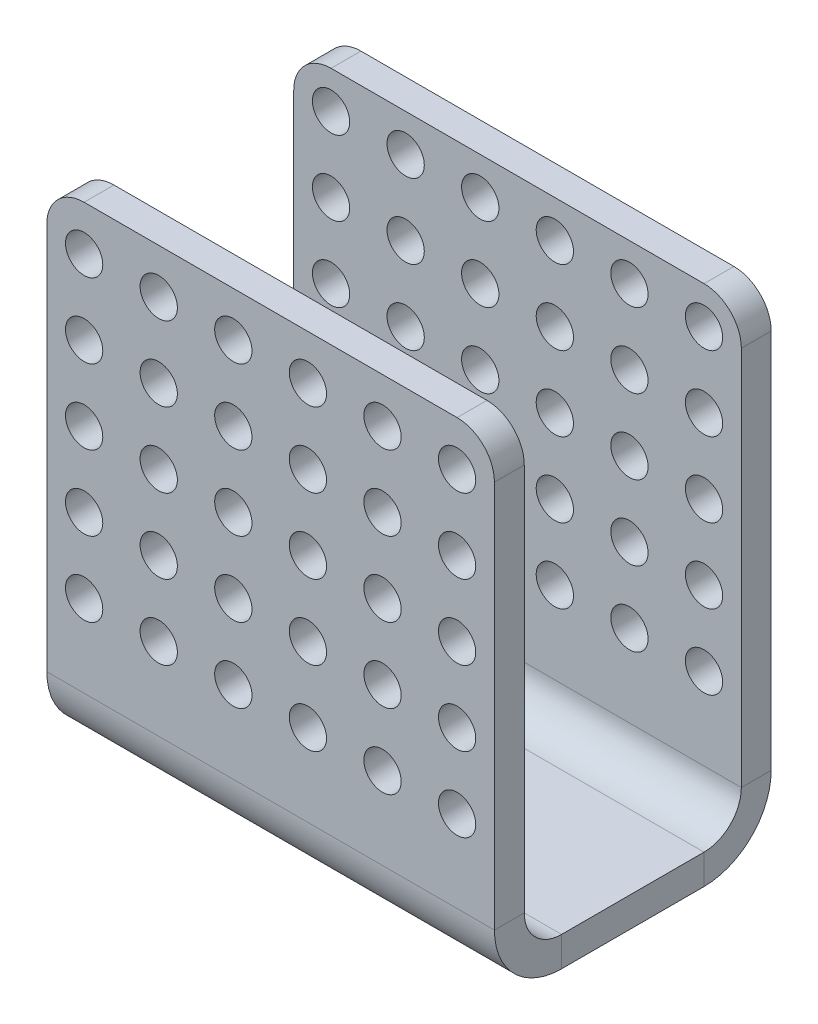
SolidWorks part; units mm, degrees
note: The reader was unsure of these and kept them because the rebuilt part matched: flange length of "Edge-Flange1", "Edge-Flange2".
ref_plane "Front Plane" through (0, 0, 0) normal (0, 0, 1) x (1, 0, 0)
ref_plane "Top Plane" through (0, 0, 0) normal (0, 1, 0) x (1, 0, 0)
ref_plane "Right Plane" through (0, 0, 0) normal (1, 0, 0) x (0, 0, -1)
sketch "Sketch2" plane through (0, 0, 0) normal (0, 1, 0) x (1, 0, 0)
  line L1 (30, -14.55) -> (-30, -14.55)
  line L2 (30, -14.55) -> (30, 14.55)
  line L3 (30, 14.55) -> (-30, 14.55)
  line L4 (-30, -14.55) -> (-30, 14.55)
  line L5 (30, -14.55) -> (-30, 14.55) construction
  line L6 (30, 14.55) -> (-30, -14.55) construction
  point P0 (0, 0)
  dimension "D1" = 29.1
  dimension "D2" = 60
base flange "Base-Flange1" sketch "Sketch2" thickness 4 reverse thickness direction no parameters "D1"=5
edge flange "Edge-Flange1" sketch "Sketch9" flange angle 90 flange length 66 flange position material outside bend radius 5 thickness 4 relief rectangular parameters "D1"=0.7366, "D6"=10
sketch "Sketch9" plane through (0, 0, 14.55) normal (0, 0, 1) x (1, 0, 0)
  line L0 (-30, 0) -> (30, 0) construction
  line L1 (-30, 0) -> (30, 0)
  line L2 (-30, 0) -> (-30, 62)
  line L3 (-30, 62) -> (30, 62)
  line L4 (30, 62) -> (30, 0)
bend "EdgeBend1" bend radius 5 bend angle 90 parameters "D5"=1
edge flange "Edge-Flange2" sketch "Sketch12" flange angle 90 flange length 65 flange position material outside bend radius 5 thickness 4 relief rectangular parameters "D6"=10
sketch "Sketch12" plane through (0, 0, -14.55) normal (0, 0, -1) x (-1, 0, 0)
  line L0 (-30, 0) -> (30, 0) construction
  line L1 (-30, 0) -> (30, 0)
  line L2 (-30, 0) -> (-30, 61)
  line L3 (-30, 61) -> (30, 61)
  line L4 (30, 61) -> (30, 0)
bend "EdgeBend2" bend radius 5 bend angle 90 parameters "D5"=2
hole_wizard "Ø1.0mm Dowel Hole1" positions "Sketch13" profile "Sketch14" hole size "Ø1.0" standard "ANSI Metric" end condition through all
sketch "Sketch13" plane through (0, 0, -18.55) normal (0, 0, -1) x (-1, 0, 0)
  line L0 (30, 61) -> (-30, 61) construction
  line L1 (-30, 61) -> (-30, 5) construction
  point P0 (-25, 56)
  dimension "D1" = 5
  dimension "D2" = 5
sketch "Sketch14" plane through (25, 56, -18.55) normal (1, 0, 0) x (0, 1, 0)
  line L0 (0, 0) -> (0, 37.1)
  line L1 (0, 37.1) -> (2.5, 37.1)
  line L2 (2.5, 37.1) -> (2.5, 0)
  line L5 (2.5, 0) -> (0, 0)
  line L11 (0, -6.35) -> (0, 107.95) construction
  dimension "Thru Hole Dia." = 5
  dimension "Thru Hole Depth" = 37.1
pattern_linear "LPattern1" count 6 spacing 10 along (-1, 0, 0) count 5 spacing 10 along (0, -1, 0) of "Ø1.0mm Dowel Hole1"
fillet "Fillet1" radius 5 4 edges at (-30, 61, -16.55) (-30, 62, 16.55) (30, 62, 16.55) (30, 61, -16.55)
sketch "Bend-Lines1" [suppressed] plane through (0, 0, 0) normal (0, 1, 0) x (1, 0, 0)
sketch "Bounding-Box1" [suppressed] plane through (0, 0, 0) normal (0, 1, 0) x (1, 0, 0)
sheet metal parameters "Sheet-Metal1" thickness 4 parameters "D1"=0.7366
flat pattern "Flat-Pattern1" [suppressed]
sketch "Bend-Lines2" plane through (0, 0, 0) normal (0, 1, 0) x (1, 0, 0)
sketch3d "Bounding-Box2" [suppressed]
  line L0 (-30, -14.55, 0) -> (30, -14.55, 0) construction
  line L1 (-30, 14.55, 0) -> (30, 14.55, 0) construction
  line L2 (-30, -14.55, 0) -> (-30, 14.55, 0) construction
  line L3 (30, -14.55, 0) -> (30, 14.55, 0) construction
sheet metal parameters "Sheet-Metal2" thickness 4 parameters "D1"=0.7366
flat pattern "Flat-Pattern1"
sketch "Bend-Lines2" plane through (0, 0, 0) normal (0, 1, 0) x (1, 0, 0)
  line L0 (-30, -15.0478) -> (30, -15.0478) construction
  line L1 (-30, -15.0478) -> (30, -15.0478) construction
sketch3d "Bounding-Box2" [suppressed]
  line L0 (-30, 14.55, 0) -> (-30, -77.5456, 0) construction
  line L1 (30, 14.55, 0) -> (30, -77.5456, 0) construction
  line L2 (-30, 14.55, 0) -> (30, 14.55, 0) construction
  line L3 (-30, -77.5456, 0) -> (30, -77.5456, 0) construction
bend of the flat pattern "Flatten-<EdgeBend1>1"
sheet metal parameters "Sheet-Metal3" thickness 4 parameters "D1"=0.7366
flat pattern "Flat-Pattern1"
sketch "Bend-Lines2" plane through (0, 0, 0) normal (0, 1, 0) x (1, 0, 0)
  line L0 (-30, -15.0478) -> (30, -15.0478) construction
  line L1 (-30, -15.0478) -> (30, -15.0478) construction
  line L2 (30, 15.0478) -> (-30, 15.0478) construction
  line L3 (30, 15.0478) -> (-30, 15.0478) construction
sketch3d "Bounding-Box2" [suppressed]
  line L0 (-30, 76.5456, 0) -> (-30, -77.5456, 0) construction
  line L1 (30, 76.5456, 0) -> (30, -77.5456, 0) construction
  line L2 (-30, 76.5456, 0) -> (30, 76.5456, 0) construction
  line L3 (-30, -77.5456, 0) -> (30, -77.5456, 0) construction
bend of the flat pattern "Flatten-<EdgeBend1>1"
bend of the flat pattern "Flatten-<EdgeBend2>1"
sheet metal parameters "Sheet-Metal4" thickness 4 parameters "D1"=0.7366
flat pattern "Flat-Pattern1"
sketch "Bend-Lines2" plane through (0, 0, 0) normal (0, 1, 0) x (1, 0, 0)
  line L0 (-30, -15.0478) -> (30, -15.0478) construction
  line L1 (-30, -15.0478) -> (30, -15.0478) construction
  line L2 (30, 15.0478) -> (-30, 15.0478) construction
  line L3 (30, 15.0478) -> (-30, 15.0478) construction
sketch3d "Bounding-Box2" [suppressed]
  line L0 (-30, 76.5456, 0) -> (-30, -77.5456, 0) construction
  line L1 (30, 76.5456, 0) -> (30, -77.5456, 0) construction
  line L2 (-30, 76.5456, 0) -> (30, 76.5456, 0) construction
  line L3 (-30, -77.5456, 0) -> (30, -77.5456, 0) construction
bend of the flat pattern "Flatten-<EdgeBend1>1"
bend of the flat pattern "Flatten-<EdgeBend2>1"
sheet metal parameters "Sheet-Metal5" thickness 4 parameters "D1"=0.7366
flat pattern "Flat-Pattern1"
sketch "Bend-Lines2" plane through (0, 0, 0) normal (0, 1, 0) x (1, 0, 0)
  line L0 (-30, -15.0478) -> (30, -15.0478) construction
  line L1 (-30, -15.0478) -> (30, -15.0478) construction
  line L2 (30, 15.0478) -> (-30, 15.0478) construction
  line L3 (30, 15.0478) -> (-30, 15.0478) construction
sketch3d "Bounding-Box2" [suppressed]
  line L0 (30, 76.5456, 0) -> (30, -77.5456, 0) construction
  line L1 (-30, 76.5456, 0) -> (-30, -77.5456, 0) construction
  line L2 (30, 76.5456, 0) -> (-30, 76.5456, 0) construction
  line L3 (30, -77.5456, 0) -> (-30, -77.5456, 0) construction
bend of the flat pattern "Flatten-<EdgeBend1>1"
bend of the flat pattern "Flatten-<EdgeBend2>1"
